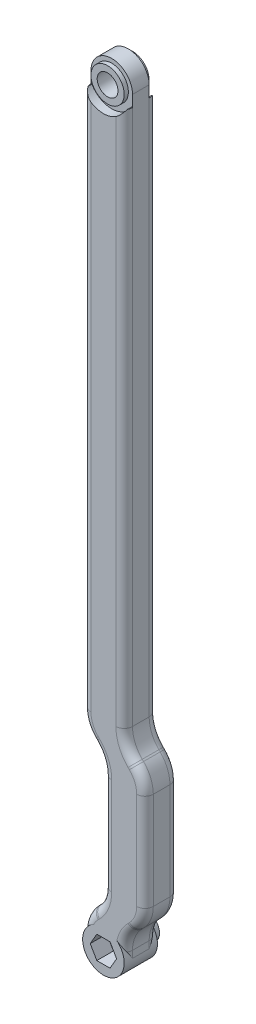
SolidWorks part; units mm, degrees
ref_plane "前视基准面" through (0, 0, 0) normal (0, 0, 1) x (1, 0, 0)
ref_plane "上视基准面" through (0, 0, 0) normal (0, 1, 0) x (1, 0, 0)
ref_plane "右视基准面" through (0, 0, 0) normal (1, 0, 0) x (0, 0, -1)
sketch "草图1" plane through (0, 0, 0) normal (0, 0, 1) x (1, 0, 0)
  line L0 (-5, -175) -> (-5, -180)
  line L1 (-5, -175) -> (0, -170)
  line L2 (0, -170) -> (0, -140)
  line L3 (0, -140) -> (-5, -135)
  line L4 (-5, -135) -> (-5, 0)
  line L8 (5, -135) -> (10, -140)
  line L9 (10, -140) -> (10, -170)
  line L10 (10, -170) -> (5, -175)
  line L12 (5, -180) -> (5, -175)
  line L13 (5, -135) -> (5, 0)
  arc A10 (-5, 0) -> (5, 0) centre (0, 0) cw
  arc A11 (5, -180) -> (-5, -180) centre (0, -180) cw
extrude "凸台-拉伸1" add sketch "草图1" along normal blind 8
fillet "圆角1" radius 8 8 edges at (-5, -135, 4) (0, -140, 4) (0, -170, 4) (-5, -175, 4) (5, -175, 4) (10, -170, 4) (10, -140, 4) (5, -135, 4)
sketch "草图2" plane through (0, 0, 0) normal (0, 0, -1) x (-1, 0, 0)
  line L0 (5, 0) -> (5, -2.75)
  line L4 (4.7631, -2.75) -> (5, -2.75)
  line L5 (5, 0) -> (5, -131.6863) construction
  line L6 (-4.7631, -2.75) -> (-5, -2.75)
  line L7 (-5, -131.6863) -> (-5, 0) construction
  line L8 (-5, -2.75) -> (-5, 0)
  arc A2 (4.7631, -2.75) -> (-4.7631, -2.75) centre (0, 0) cw
  arc A3 (5, 0) -> (-5, 0) centre (0, 0) ccw
extrude "切除-拉伸1" cut sketch "草图2" against normal blind 1
sketch "草图3" plane through (0, 0, 1) normal (0, 0, -1) x (-1, 0, 0)
  circle A0 centre (0, 0) radius 2.5
extrude "凸台-拉伸2" add sketch "草图3" along normal blind 4
sketch "草图4" plane through (0, 0, 1) normal (0, 0, -1) x (-1, 0, 0)
  line L0 (-5, 0) -> (-5, -2.75) construction
  line L1 (-5, 0) -> (-5, -2.75)
  line L2 (-5, -2.75) -> (-4.7631, -2.75)
  line L3 (4.7631, -2.75) -> (5, -2.75)
  line L4 (5, -2.75) -> (5, 0)
  circle A0 centre (0, 0) radius 4
  arc A1 (5, 0) -> (-5, 0) centre (0, 0) ccw
  arc A2 (-4.7631, -2.75) -> (4.7631, -2.75) centre (0, 0) ccw
  arc A3 (-4.7631, -2.75) -> (4.7631, -2.75) centre (0, 0) ccw construction
extrude "切除-拉伸3" cut sketch "草图4" against normal blind 1
sketch "草图5" plane through (0, 0, 8) normal (0, 0, 1) x (1, 0, 0)
  circle A0 centre (0, 0) radius 2.5
extrude "切除-拉伸4" cut sketch "草图5" against normal up to next
extrude "切除-拉伸5" cut sketch "草图4<2>" along normal blind 2 from surface starting at face at (2.5, 0, 8)
sketch "草图4<2>" plane through (0, 0, 1) normal (0, 0, -1) x (-1, 0, 0) same geometry as "草图4"
sketch "草图7" plane through (0, 0, 8) normal (0, 0, 1) x (1, 0, 0)
  circle A0 centre (0, 0) radius 4
extrude "切除-拉伸6" cut sketch "草图7" against normal blind 1
fillet "圆角2" radius 2 38 edges at (-4.391, -134.7478, 0) (-2.5, -137.5, 0) (-0.609, -140.2522, 0) (0, -155, 0) (-0.609, -169.7478, 0) (-2.5, -172.5, 0) (-4.391, -175.2522, 0) (-5, -179.1569, 0) (0, -185, 0) (5, -179.1569, 0) (5.609, -175.2522, 0) (7.5, -172.5, 0) (9.391, -169.7478, 0) (10, -155, 0) (9.391, -140.2522, 0) (7.5, -137.5, 0) (5.609, -134.7478, 0) (-4.391, -134.7478, 8) (-2.5, -137.5, 8) (-0.609, -140.2522, 8) (0, -155, 8) (-0.609, -169.7478, 8) (-2.5, -172.5, 8) (-4.391, -175.2522, 8) (-5, -179.1569, 8) (0, -185, 8) (5, -179.1569, 8) (5.609, -175.2522, 8) (7.5, -172.5, 8) (9.391, -169.7478, 8) (10, -155, 8) (9.391, -140.2522, 8) (7.5, -137.5, 8) (5.609, -134.7478, 8) (-5, -67.2181, 0) (5, -67.2181, 0) (-5, -67.2181, 8) (5, -67.2181, 8)
sketch "草图9" plane through (0, 0, 8) normal (0, 0, 1) x (1, 0, 0)
  circle A0 centre (0, -180) radius 5
extrude "凸台-拉伸3" add sketch "草图9" against normal blind 8
sketch "草图11" plane through (0, 0, 0) normal (0, 0, -1) x (-1, 0, 0)
  circle A0 centre (0, -180) radius 3
extrude "凸台-拉伸4" add sketch "草图11" along normal blind 2.5
fillet "圆角3" radius 1 1 edges at (-3, -180, 0)
sketch "草图12" plane through (0, 0, -2.5) normal (0, 0, -1) x (-1, 0, 0)
  circle A0 centre (0, -180) radius 1.6
extrude "切除-拉伸8" cut sketch "草图12" against normal blind 12
sketch "草图13" plane through (0, 0, 8) normal (0, 0, 1) x (1, 0, 0)
  line L40 (-1.5877, -177.25) -> (-3.1754, -180)
  line L41 (-3.1754, -180) -> (-1.5877, -182.75)
  line L42 (-1.5877, -182.75) -> (1.5877, -182.75)
  line L43 (1.5877, -182.75) -> (3.1754, -180)
  line L44 (3.1754, -180) -> (1.5877, -177.25)
  line L45 (1.5877, -177.25) -> (-1.5877, -177.25)
  circle A2 centre (0, -180) radius 2.75 construction
extrude "切除-拉伸9" cut sketch "草图13" against normal blind 4
